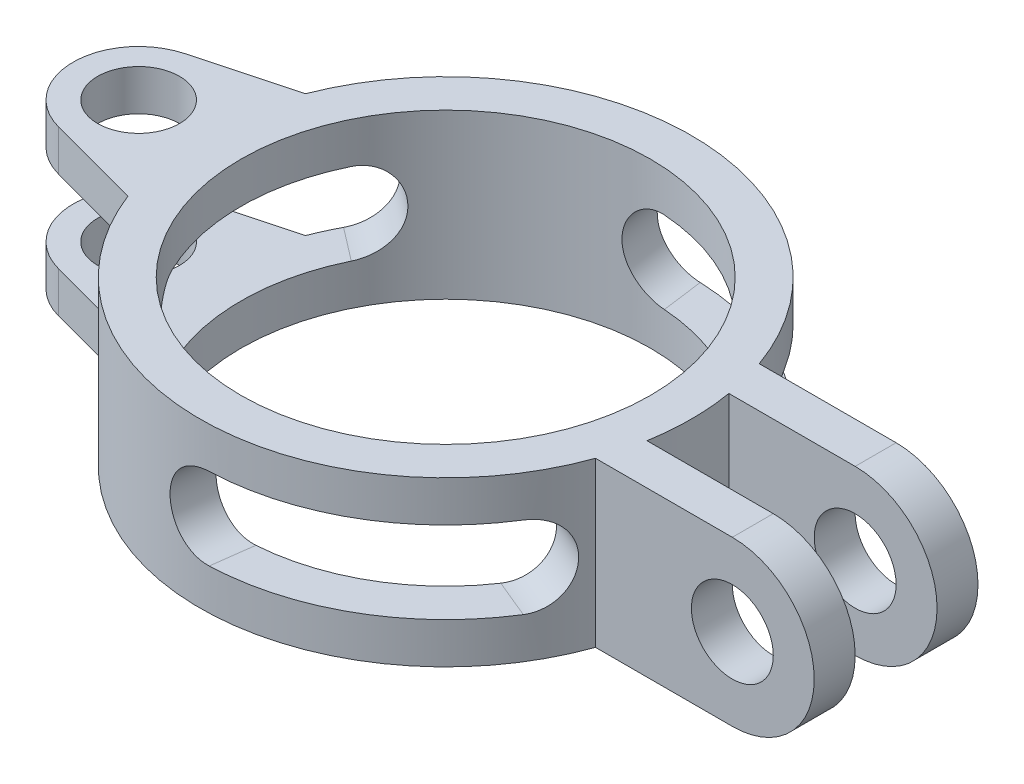
SolidWorks part; units mm, degrees
ref_plane "Front Plane" through (0, 0, 0) normal (0, 0, 1) x (1, 0, 0)
ref_plane "Top Plane" through (0, 0, 0) normal (0, 1, 0) x (1, 0, 0)
ref_plane "Right Plane" through (0, 0, 0) normal (1, 0, 0) x (0, 0, -1)
sketch "Sketch1" plane through (0, 0, 0) normal (0, 1, 0) x (1, 0, 0)
  circle A0 centre (0, 0) radius 30
  circle A1 centre (0, 0) radius 25
  dimension "D1" = 60
  dimension "D2" = 50
extrude "Boss-Extrude1" add sketch "Sketch1" along normal mid plane 20
sketch "Sketch3" plane through (0, 10, 0) normal (0, 1, 0) x (1, 0, 0)
  line L0 (0, 0) -> (-37.5, 0) construction
  line L1 (-39.5706, 7.7274) -> (-27.9753, 10.8343)
  line L2 (-39.5706, -7.7274) -> (-27.9753, -10.8343)
  line L3 (0, 0) -> (51.7248, 0) construction
  line L5 (28.2843, 10) -> (55, 10)
  line L7 (29.5804, 5) -> (55, 5)
  line L8 (55, 5) -> (55, 10)
  line L9 (29.5804, -5) -> (55, -5)
  line L10 (55, -5) -> (55, -10)
  line L11 (55, -10) -> (28.2843, -10)
  circle A0 centre (0, 0) radius 37.5 construction
  circle A1 centre (-37.5, 0) radius 5
  arc A3 (-27.9753, 10.8343) -> (-27.9753, -10.8343) centre (0, 0) ccw
  arc A4 (-39.5706, 7.7274) -> (-39.5706, -7.7274) centre (-37.5, 0) ccw
  circle A5 centre (0, 0) radius 30 construction
  arc A6 (28.2843, 10) -> (29.5804, 5) centre (0, 0) cw
  arc A7 (29.5804, -5) -> (28.2535, -10.0865) centre (0, 0) cw
  circle M5 centre (0, 0) radius 30
  dimension "D1" = 75
  dimension "D2" = 8
  dimension "D3" = 10
  dimension "D4" = 60
  dimension "D5" = 15
  dimension "D6" = 15
  dimension "D7" = 20
  dimension "D8" = 10
  dimension "D9" = 5
  dimension "D10" = 5
  dimension "D11" = 55
  dimension "D12" = 55
extrude "Boss-Extrude2" add sketch "Sketch3" against normal blind 5 contours L1 A4 L2 A1 M5 region at (-33.7008, 10, -9.0117)
extrude "Boss-Extrude3" add sketch "Sketch3<3>" against normal blind 20 contours L7 L8 L5 M5 | L11 L10 L9 M5 region at (42.0018, 10, -7.5207) region at (42.0018, 10, 7.5207)
sketch "Sketch3<3>" plane through (0, 10, 0) normal (0, 1, 0) x (1, 0, 0) same geometry as "Sketch3"
mirror "Mirror1" about plane through (0, 0, 0) normal (0, 1, 0) of "Boss-Extrude2"
sketch "Sketch4" plane through (0, 0, 0) normal (0, 1, 0) x (1, 0, 0)
  line L0 (0, 0) -> (15, -25.9808) construction
  line L1 (0, 0) -> (23.097, -9.5671) construction
  line L2 (0, 0) -> (-3.2632, -24.7861) construction
  line L3 (0, 0) -> (-37.5, 0) construction
  line L4 (0, 0) -> (15, 25.9808) construction
  line L5 (0, 0) -> (-19.8338, -15.219) construction
  line L6 (0, 0) -> (-19.8338, 15.219) construction
  line L7 (0, 0) -> (-3.2632, 24.7861) construction
  line L8 (0, 0) -> (23.097, 9.5671) construction
  line L9 (-3.2632, -24.7861) -> (-3.9158, -29.7433)
  line L10 (23.097, -9.5671) -> (27.7164, -11.4805)
  line L11 (23.097, 9.5671) -> (27.7164, 11.4805)
  line L12 (-3.2632, 24.7861) -> (-3.9158, 29.7433)
  line L13 (-19.8338, 15.219) -> (-23.8006, 18.2628)
  line L14 (-19.8338, -15.219) -> (-23.8006, -18.2628)
  circle A0 centre (0, 0) radius 30 construction
  arc A2 (-23.8006, 18.2628) -> (-23.8006, -18.2628) centre (0, 0) ccw
  circle A3 centre (0, 0) radius 30 construction
  arc A4 (-19.8338, 15.219) -> (-19.8338, -15.219) centre (0, 0) ccw
  circle A5 centre (0, 0) radius 25 construction
  arc A6 (-3.9158, 29.7433) -> (27.7164, 11.4805) centre (0, 0) cw
  arc A7 (-3.2632, 24.7861) -> (23.097, 9.5671) centre (0, 0) cw
  arc A8 (27.7164, -11.4805) -> (-3.9158, -29.7433) centre (0, 0) cw
  arc A9 (23.097, -9.5671) -> (-3.2632, -24.7861) centre (0, 0) cw
  arc A10 (28.2843, 10) -> (-27.9753, 10.8343) centre (0, 0) ccw construction
  point P12 (18.75, 32.476)
  point P13 (14.6512, 25.4642)
  point P23 (15.017, -25.971)
  point P24 (15, 25.9808)
  dimension "D1" = 37.5
  dimension "D2" = 75
  dimension "D3" = 37.5
  dimension "D4" = 37.5
  dimension "D5" = 75
  dimension "D6" = 37.5
  dimension "D7" = 37.5
  dimension "D8" = 75
  dimension "D9" = 37.5
  dimension "D10" = 120
  dimension "D11" = 120
extrude "Cut-Extrude1" cut sketch "Sketch4" against normal mid plane 10 contours A4 L13 A2 L14 | L10 A9 L9 A8 | L12 A7 L11 A6 region at (12.8244, 0, 22.2125) region at (12.8244, 0, -22.2125) region at (-25.6487, 0, 0)
sketch "Sketch5" plane through (0, 0, 10) normal (0, 0, 1) x (1, 0, 0)
  line L0 (0, 0) -> (59.192, 0) construction
  circle A0 centre (45, 0) radius 5
  circle A1 centre (45, 0) radius 10
  line M1 (55, 10) -> (28.2843, 10)
  line M3 (28.2843, -10) -> (55, -10)
  line M4 (55, -10) -> (55, 10)
  dimension "D2" = 10
  dimension "D3" = 20
  dimension "D1" = 45
extrude "Cut-Extrude2" cut sketch "Sketch5" against normal up to surface (20 mm away) contours A1 M4 M1 | A1 M3 M4 | A0 L0 | L0 A0 region at (45, -2.1221, 10) region at (45, 2.1221, 10) region at (52.7663, -7.7663, 10) region at (52.7663, 7.7663, 10) up to face at (41.6421, 0, -10)
fillet "Fillet1" 2 edges at (-3.5895, 5, 27.2647) (-3.5895, -5, 27.2647) type full round first side face at (12.3293, 5, 21.355) second side face at (12.3293, -5, 21.355) middle face at (-3.5895, 0, 27.2647)
fillet "Fillet2" 2 edges at (25.4067, 5, 10.5238) (25.4067, -5, 10.5238) type full round first side face at (14.6419, 5, 20.7257) second side face at (14.6419, -5, 20.7257) middle face at (25.4067, 0, 10.5238)
fillet "Fillet3" 2 edges at (25.4067, 5, -10.5238) (25.4067, -5, -10.5238) type full round first side face at (12.3293, 5, -21.355) second side face at (12.3293, -5, -21.355) middle face at (25.4067, 0, -10.5238)
fillet "Fillet4" 2 edges at (-3.5895, 5, -27.2647) (-3.5895, -5, -27.2647) type full round first side face at (10.628, 5, -23.0431) second side face at (10.628, -5, -23.0431) middle face at (-3.5895, 0, -27.2647)
fillet "Fillet5" 2 edges at (-21.8172, 5, -16.7409) (-21.8172, -5, -16.7409) type full round first side face at (-37.5, 5, 5) second side face at (-37.5, -5, 5) middle face at (-21.8172, 0, -16.7409)
fillet "Fillet6" 2 edges at (-21.8172, 5, 16.7409) (-21.8172, -5, 16.7409) type full round first side face at (-37.5, 5, 5) second side face at (-37.5, -5, 5) middle face at (-21.8172, 0, 16.7409)
